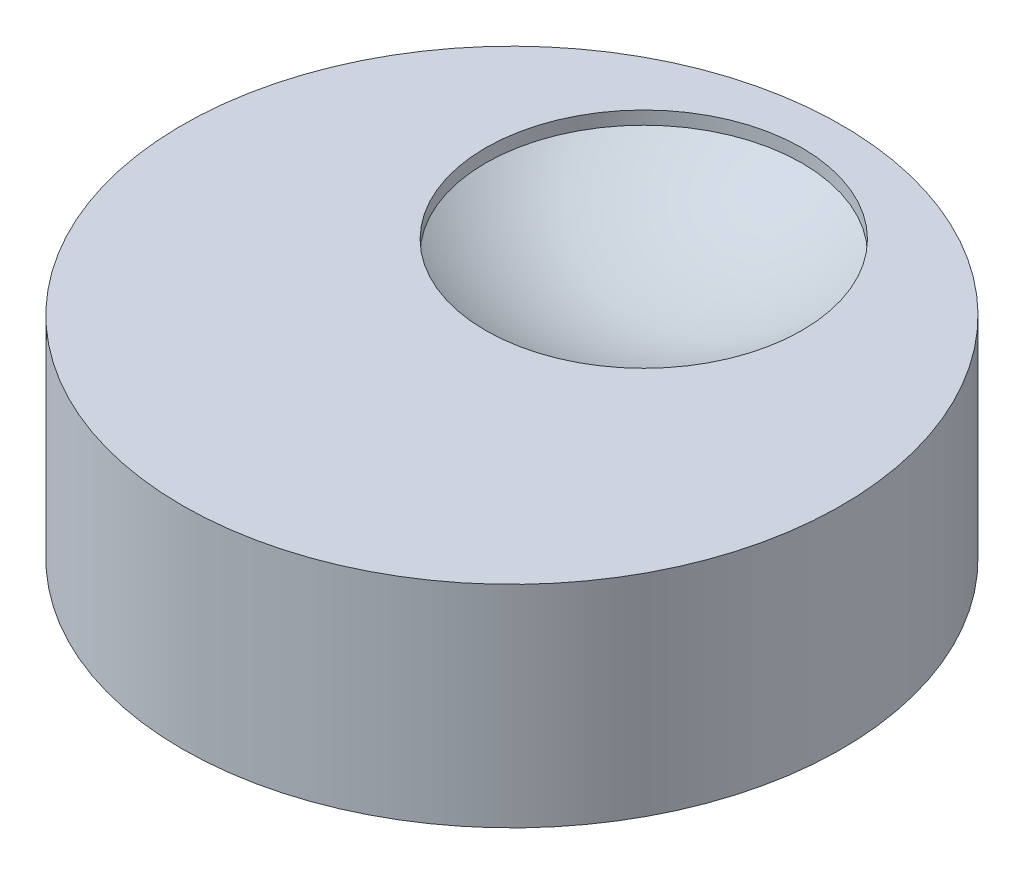
SolidWorks part; units mm, degrees
material "Printed PLA"
ref_plane "Front Plane" through (0, 0, 0) normal (0, 0, 1) x (1, 0, 0)
ref_plane "Top Plane" through (0, 0, 0) normal (0, 1, 0) x (1, 0, 0)
ref_plane "Right Plane" through (0, 0, 0) normal (1, 0, 0) x (0, 0, -1)
sketch "Sketch1" plane through (0, 0, 0) normal (0, 1, 0) x (1, 0, 0)
  line L0 (-2.8583, -1.2) -> (2.8583, -1.2)
  circle A0 centre (0, 0) radius 12.5
  arc A1 (2.8583, -1.2) -> (-2.8583, -1.2) centre (0, 0) ccw
  dimension "D1" = 3.1
  dimension "D3" = 25
  dimension "D2" = 1.2
extrude "Boss-Extrude1" add sketch "Sketch1" along normal blind 8
sketch "Sketch2" plane through (0, 8, 0) normal (0, 1, 0) x (1, 0, 0)
  circle A0 centre (0, 0) radius 12.5
  circle A1 centre (0, 0) radius 12.5 construction
extrude "Boss-Extrude2" add sketch "Sketch2" against normal blind 3
sketch "Sketch3" plane through (0, 8, 0) normal (0, 1, 0) x (1, 0, 0)
  line L0 (0, 5) -> (0, 0) construction
  circle A0 centre (0, 5) radius 6
  dimension "D1" = 12
  dimension "D2" = 5
extrude "Cut-Extrude1" cut sketch "Sketch3" against normal blind 0.5
dome "Dome1" faces to dome 1 distance 2 reverse direction yes elliptical dome no face at (0, 7.5, 1) parameters "D1"=2
